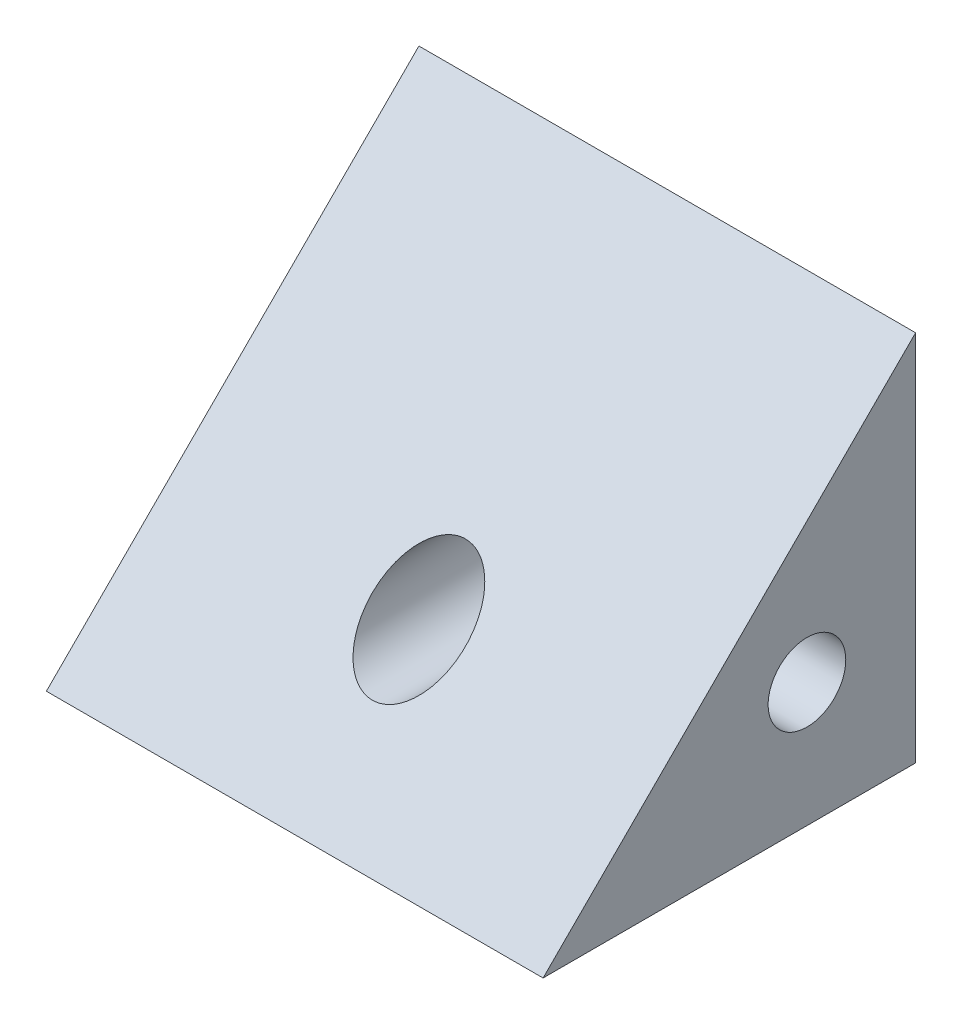
SolidWorks part; units mm, degrees
ref_plane "Face" through (0, 0, 0) normal (0, 0, 1) x (1, 0, 0)
ref_plane "Dessus" through (0, 0, 0) normal (0, 1, 0) x (1, 0, 0)
ref_plane "Droite" through (0, 0, 0) normal (1, 0, 0) x (0, 0, -1)
sketch "Esquisse1" plane through (0, 0, 0) normal (0, 0, 1) x (1, 0, 0)
  line L1 (0, 0) -> (16, 0)
  line L2 (0, 0) -> (0, 12)
  line L3 (0, 12) -> (16, 12)
  line L4 (16, 0) -> (16, 12)
  dimension "D1" = 12
  dimension "D2" = 16
extrude "Extrusion1" add sketch "Esquisse1" along normal blind 14
chamfer "Chanfrein1" distance 14 angle 45 1 edges at (8, 12, 14)
sketch "Esquisse2" plane through (0, 0, 0) normal (0, -1, 0) x (1, 0, 0)
  line L0 (0, 12) -> (16, 12) construction
  line L2 (16, 12) -> (16, 0) construction
  circle A0 centre (9, 5) radius 1
  dimension "D1" = 2
  dimension "D2" = 7
  dimension "D3" = 7
extrude "Enlèv. mat.-Extru.1" [suppressed] cut sketch "Esquisse2" against normal through all
sketch "Esquisse3" plane through (0, 0, 0) normal (0, 0, -1) x (-1, 0, 0)
  line L0 (-16, 12) -> (0, 12) construction
  line L1 (0, 0) -> (-16, 0) construction
  line L2 (0, 12) -> (0, 0) construction
  circle A0 centre (-8, 4) radius 1.5
  dimension "D1" = 3
  dimension "D2" = 8
  dimension "D3" = 4
  dimension "D4" = 8
extrude "Enlèv. mat.-Extru.2" cut sketch "Esquisse3" against normal through all
hole_wizard "Trou taraudé M3x0.51" positions "Esquisse5" profile "Esquisse6" tap size "M3x0.5" standard "Ansi Métrique" end condition through all
sketch "Esquisse5" plane through (16, 0, 0) normal (1, 0, 0) x (0, 0, -1)
  line L0 (-12, 0) -> (0, 0) construction
  line L1 (0, 0) -> (0, 12) construction
  point P0 (-3.5, 4)
  dimension "D1" = 4
  dimension "D2" = 3.5
sketch "Esquisse6" plane through (16, 4, 3.5) normal (0, 1, 0) x (0, 0, -1)
  line L0 (0, 0) -> (0, 16)
  line L1 (0, 16) -> (1.25, 16)
  line L2 (1.25, 16) -> (1.25, 0)
  line L5 (1.25, 0) -> (0, 0)
  line L11 (0, -6.35) -> (0, 107.95) construction
  dimension "Diamètre du trou pour taraudage jusqu'au prochain" = 2.5
  dimension "Profondeur du trou pour taraudage jusqu'au prochain" = 16
cosmetic thread "Filetage de perçage1"
